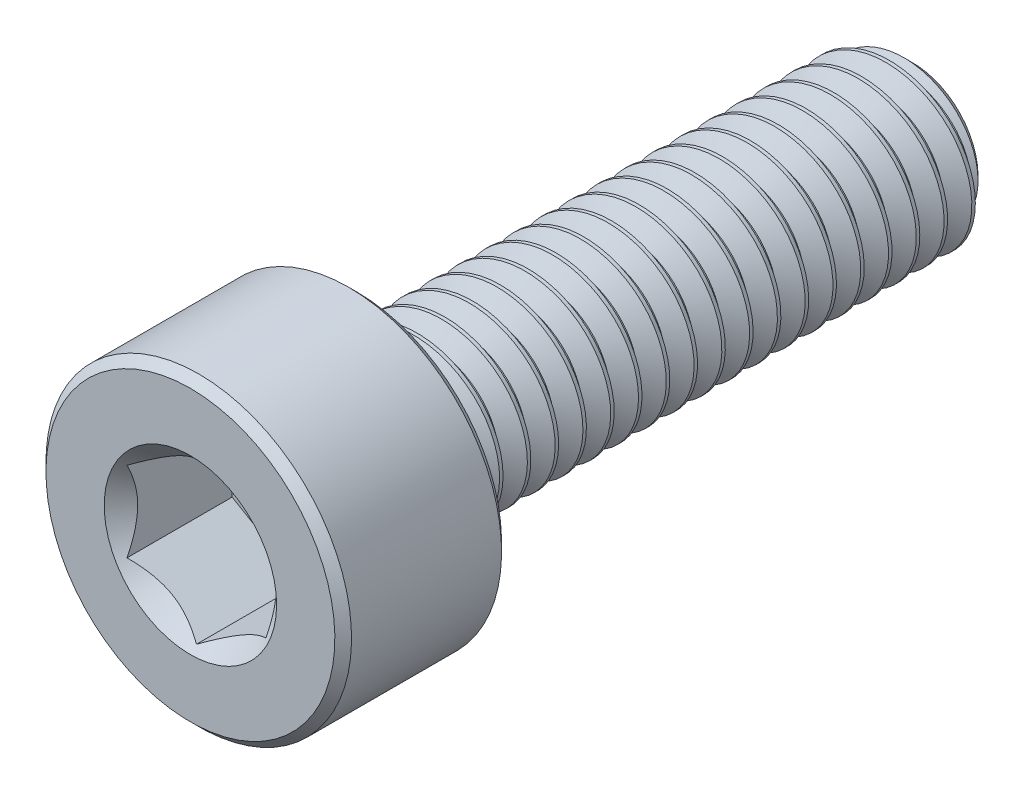
SolidWorks part; units mm, degrees
ref_plane "Front Plane" through (0, 0, 0) normal (0, 0, 1) x (1, 0, 0)
ref_plane "Top Plane" through (0, 0, 0) normal (0, 1, 0) x (1, 0, 0)
ref_plane "Right Plane" through (0, 0, 0) normal (1, 0, 0) x (0, 0, -1)
sketch "Sketch1" plane through (0, 0, 0) normal (1, 0, 0) x (0, 0, -1)
  line L0 (-6.5, 0) -> (6.5, 0) construction
  line L1 (6.5, 0) -> (6.5, 1.1752) construction
  line L2 (6.5, 1.1752) -> (6.1752, 1.5) construction
  line L3 (6.1752, 1.5) -> (6.125, 1.5) construction
  line L4 (6.125, 1.5) -> (-3.5, 1.5) construction
  line L5 (-3.5, 1.5) -> (-3.5, 2.75) construction
  line L6 (-3.5, 2.75) -> (-6.5, 2.75) construction
  line L7 (-6.5, 2.75) -> (-6.5, 0) construction
  line L8 (6.5, 1.1752) -> (6.5, 1.5) construction
  line L9 (6.4687, 1.5541) -> (6.7187, 1.1211) construction
  line L10 (6.7187, 1.1211) -> (6.9687, 1.5541) construction
  line L11 (6.9687, 1.5541) -> (6.4687, 1.5541) construction
  line L12 (6.7187, 1.5541) -> (6.7188, 1.5) construction
  line L13 (6.7187, 1.1211) -> (6.7187, 1.1752) construction
  line L14 (6.6875, 1.1752) -> (6.75, 1.1752) construction
  line L15 (6.5, 1.5) -> (6.9375, 1.5) construction
  line L16 (6.4844, 1.5271) -> (6.9531, 1.5271) construction
  line L17 (6.5, 0) -> (6.5, -1.5) construction
  line L18 (-3.65, 2.75) -> (-3.5, 2.6) construction
  line L19 (-6.35, 2.75) -> (-6.5, 2.6) construction
  line L20 (-3.5, 1.5) -> (-3.5, 0) construction
  line L21 (-3.5, 0.75) -> (-0.1667, 0.75) construction
  line L22 (-0.1667, 0.75) -> (3.1667, 0.75) construction
  line L23 (3.1667, 0.75) -> (6.5, 0.75) construction
  line L24 (-0.1667, 0.75) -> (-0.1667, 1.5) construction
  line L25 (-0.1667, 1.5) -> (-0.1667, 2.75) construction
  line L26 (3.1667, 0.75) -> (3.1667, 2.75) construction
  point P0 (-6.5, 1.25)
  point P3 (5.25, 1.5)
  point P4 (0, 0)
  point P18 (3.1667, 1.5)
  point P22 (6.7187, 1.1752)
  point P24 (6.125, 1.5)
  point P25 (6.7188, 1.5)
  point P28 (6.7188, 1.5271)
  point P29 (5.25, -1.5)
  point P30 (-0.1667, 1.5)
  point P31 (-5, 2.75)
  point P37 (-4.025, 2.75)
  point P38 (-6.275, 2.75)
  point P45 (-0.1667, 0.75)
  point P46 (3.1667, 0.75)
  dimension "D2" = 0.0625
  dimension "D7" = 0.15
  dimension "D8" = 0.15
  dimension "D9" = 0.15
  dimension "D10" = 0.075
  dimension "D11" = 0.375
  dimension "Drive Size" = 2.5
  dimension "Head Diameter" = 5.5
  dimension "Head Height" = 3
  dimension "Thread Pitch" = 0.5
  dimension "Thread Size" = 3
  dimension "Length" = 10
  dimension "D12" = 0.375
  dimension "D4" = 1.25
  dimension "D3" = 45
sketch "Sketch2" plane through (0, 0, 0) normal (1, 0, 0) x (0, 0, -1)
  line L0 (-6.5, 0) -> (-6.5, 2.6)
  line L1 (-6.35, 2.75) -> (-3.65, 2.75)
  line L2 (-3.5, 2.6) -> (-3.5, 1.65)
  line L4 (6.1752, 1.5) -> (6.5, 1.1752)
  line L5 (6.5, 1.1752) -> (6.5, 0)
  line L6 (-3.5, 2.75) -> (-6.5, 2.75) construction
  line L7 (6.5, 0) -> (-6.5, 0)
  line L8 (-6.35, 2.75) -> (-6.5, 2.6) construction
  line L10 (-6.35, 2.75) -> (-6.5, 2.6)
  line L14 (-3.65, 2.75) -> (-3.5, 2.6) construction
  line L16 (-3.65, 2.75) -> (-3.5, 2.6)
  line L17 (-3.5, 1.5) -> (-3.5, 2.75) construction
  line L19 (-3.35, 1.5) -> (6.1752, 1.5)
  line L20 (6.125, 1.5) -> (-3.5, 1.5) construction
  arc A1 (-3.5, 1.65) -> (-3.35, 1.5) centre (-3.35, 1.65) ccw
  dimension "D3" = 0.15
revolve "Revolve1" add sketch "Sketch2" angle 360 about L7
sketch "Sketch3" plane through (0, 0, 6.5) normal (0, 0, 1) x (1, 0, 0)
  line L1 (1.25, -0.7217) -> (1.25, 0.7217)
  line L2 (1.25, 0.7217) -> (0, 1.4434)
  line L3 (0, 1.4434) -> (-1.25, 0.7217)
  line L4 (-1.25, 0.7217) -> (-1.25, -0.7217)
  line L5 (-1.25, -0.7217) -> (0, -1.4434)
  line L6 (0, -1.4434) -> (1.25, -0.7217)
  circle A0 centre (0, 0) radius 1.25 construction
  circle A1 centre (0, 0) radius 2.75 construction
  circle A2 centre (0, 0) radius 2.75 construction
  circle A3 centre (0, 0) radius 1.4434 construction
  point P13 (0, 0)
  dimension "D1" = 2.8868
extrude "Cut-Extrude1" cut sketch "Sketch3" against normal offset from surface (2 mm away) 1 up to face at (0, 2.6, 3.5)
sketch "Sketch4" plane through (0, 0, 6.5) normal (0, 0, 1) x (1, 0, 0)
  circle A0 centre (0, 0) radius 1.5516
  dimension "D1" = 3.1033
extrude "Cut-Extrude2" cut sketch "Sketch4" against normal up to vertex (1.5 mm away) draft 45 up to point (0, 2.75, 5)
sketch "Sketch11" plane through (0, 0, 0) normal (1, 0, 0) x (0, 0, -1)
  line L0 (-6.5, 0) -> (6.5, 0) construction
  line L1 (-6.5, 0) -> (6.5, 0) construction
  line L2 (-1.625, 0) -> (-1.625, 1.5) construction
  line L3 (6.125, 1.5) -> (-3.5, 1.5) construction
  line L4 (4.625, 0) -> (4.625, 1.5) construction
  line L6 (6.5, 1.1752) -> (6.5, 1.5) construction
  point P2 (-1.625, 0)
  point P3 (4.625, 0)
  dimension "D1" = 1.875
  dimension "D2" = 1.875
sketch "Sketch6" plane through (0, 0, -6.5) normal (0, 0, -1) x (-1, 0, 0)
  circle A0 centre (0, 0) radius 1.5
curve "Helix/Spiral1" pitch 0.5 height 10.5 turns 21
sketch "Sketch10" plane through (0, 0, 0) normal (1, 0, 0) x (0, 0, -1)
  line L0 (-3.35, -2.75) -> (-3.35, 2.75)
  line L5 (-6.5, 0) -> (6.5, 0) construction
  line L6 (-3.35, 1.5) -> (-3.35, -1.5) construction
  point P3 (-3.35, 0)
split "Split1" trim tools "Sketch10" bodies to split 106 resulting bodies 114 115
sketch "Sketch7" plane through (0, 0, 0) normal (1, 0, 0) x (0, 0, -1)
  line L0 (6.4844, 1.5271) -> (6.9531, 1.5271)
  line L1 (6.9531, 1.5271) -> (6.75, 1.1752)
  line L2 (6.75, 1.1752) -> (6.6875, 1.1752)
  line L3 (6.6875, 1.1752) -> (6.4844, 1.5271)
sweep "Cut-Sweep1" cut profiles "Sketch7" path "Helix/Spiral1" align with end faces yes
sketch "Sketch8" plane through (0, 0, 0) normal (1, 0, 0) x (0, 0, -1)
  line L0 (-3.5, 0) -> (-3.5, 1.5)
  line L1 (-3.35, -1.5) -> (-3.35, 1.5) construction
  line L2 (-3.5, 1.5) -> (-3.35, 1.5)
  line L4 (-3.35, 1.5) -> (-2.484, 0)
  line L5 (-2.484, 0) -> (-3.5, 0)
  line L6 (6.125, 1.5) -> (-3.5, 1.5) construction
  line L7 (-6.5, 0) -> (6.5, 0) construction
  dimension "D1" = 60
revolve "Revolve2" add sketch "Sketch8" angle 360 about L5
equation "\"D2@Sketch1\" = \"Thread Pitch@Sketch1\" / 8"
equation "\"D4@Helix/Spiral1\" = \"Thread Pitch@Sketch1\""
equation "\"D7@Sketch1\" = \"Head Height@Sketch1\" * .05"
equation "\"D8@Sketch1\"=\"D7@Sketch1\""
equation "\"D9@Sketch1\"=\"D7@Sketch1\""
equation "\"D10@Sketch1\"=\"D7@Sketch1\"/2"
equation "\"D11@Sketch1\"=\"D10@Sketch1\"*5"
equation "\"D4@Sketch1\"=\"Thread Pitch@Sketch1\"*2.5"
equation "\"D12@Sketch1\"=\"Thread Pitch@Sketch1\"*.75"
equation "\"D3@Helix/Spiral1\"=\"Length@Sketch1\"+\"Thread Pitch@Sketch1\""
equation "\"D3@Sketch2\"=\"Thread Size@Sketch1\"*0.05"
equation "\"D1@Sketch11\"=\"Length@Sketch1\"*0.1875"
equation "\"D2@Sketch11\"=\"D1@Sketch11\""
equation "\"D1@Sketch4\"=\"D1@Sketch3\"*1.075"
